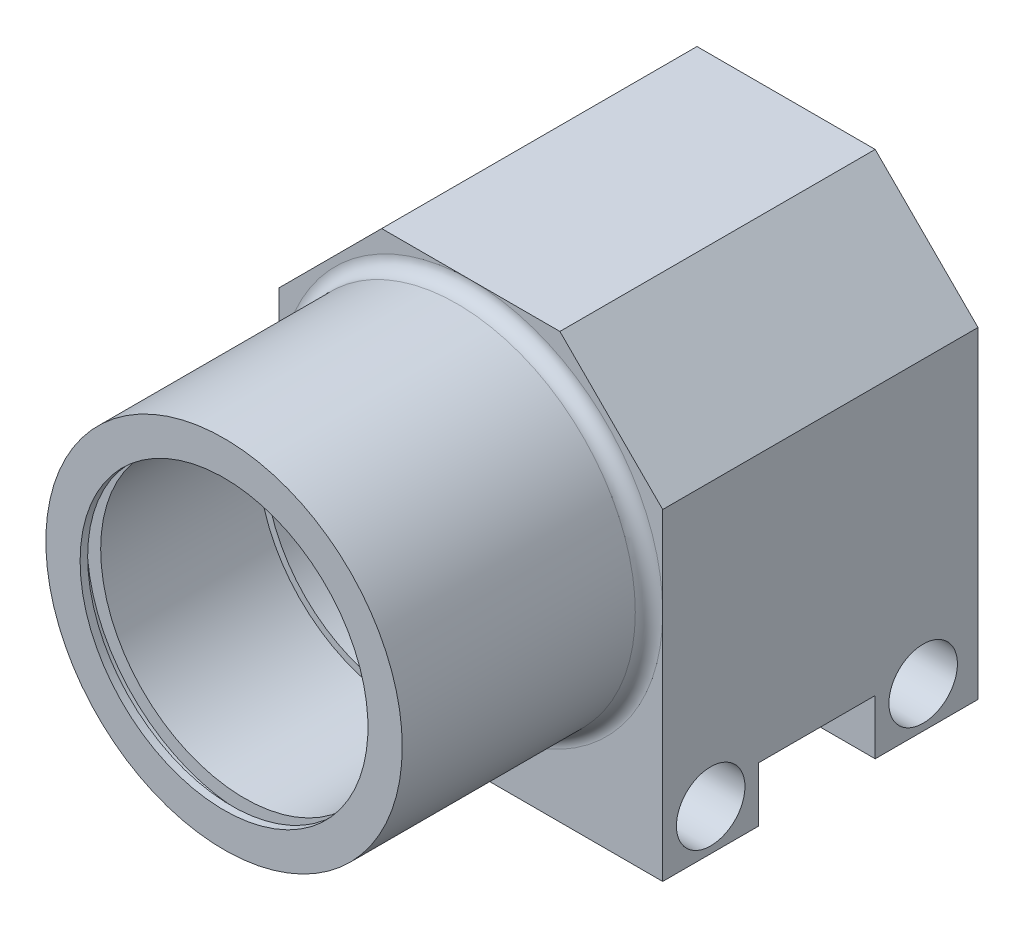
SolidWorks part; units mm, degrees
material "1060 合金"
ref_plane "前视基准面" through (0, 0, 0) normal (0, 0, 1) x (1, 0, 0)
ref_plane "上视基准面" through (0, 0, 0) normal (0, 1, 0) x (1, 0, 0)
ref_plane "右视基准面" through (0, 0, 0) normal (1, 0, 0) x (0, 0, -1)
sketch "草图1" plane through (0, 0, 0) normal (0, 0, 1) x (1, 0, 0)
  line L0 (0, -34) -> (0, 33.0223) construction
  line L1 (-28, -34) -> (28, -34)
  line L2 (-28, -34) -> (-28, 28)
  line L3 (-28, 28) -> (28, 28)
  line L4 (28, -34) -> (28, 28)
  line L5 (0, 0) -> (56.6994, 0) construction
  circle A0 centre (0, 0) radius 24 construction
  point P9 (0, 24)
  point P10 (0, -24)
  point P12 (24, 0)
  dimension "D1" = 10
  dimension "D2" = 48
  dimension "D3" = 4
  dimension "D4" = 4
extrude "凸台-拉伸1" add sketch "草图1" along normal blind 82
sketch "草图3" plane through (0, 0, 0) normal (1, 0, 0) x (0, 0, -1)
  line L0 (5.7193, 0) -> (-112.2198, 0) construction
  line L1 (0, -34) -> (0, 28) construction
  line L2 (-82, 0) -> (0, 0)
  line L3 (-82, 28) -> (-82, -34) construction
  line L4 (-82, 21) -> (-56, 21)
  line L5 (0, 0) -> (0, 23)
  line L7 (-52, 23) -> (0, 23)
  line L9 (-56, 21) -> (-56, 20)
  line L10 (-56, 20) -> (-52, 20)
  line L11 (-52, 23) -> (-52, 20)
  line L12 (-82, 0) -> (-82, 21)
  dimension "D1" = 20
  dimension "D2" = 21
  dimension "D3" = 4
  dimension "D4" = 23
  dimension "D5" = 26
revolve "切除-旋转2" cut sketch "草图3" angle 360 about L0
sketch "草图4" plane through (0, 0, 82) normal (0, 0, 1) x (1, 0, 0)
  line L0 (28, 28) -> (-28, 28) construction
  line L1 (-28, 28) -> (-28, -34) construction
  line L2 (-28, -34) -> (28, -34) construction
  line L3 (28, -34) -> (28, 28) construction
  line L4 (28, 28) -> (-28, 28)
  line L5 (-28, 28) -> (-28, -34)
  line L6 (-28, -34) -> (28, -34)
  line L7 (28, -34) -> (28, 28)
  circle A2 centre (0, 0) radius 26
  dimension "D1" = 52
chamfer "倒角1" distance 15 angle 45 2 edges at (28, 28, 41) (-28, 28, 41)
extrude "切除-拉伸1" cut sketch "草图4" against normal blind 36
hole_wizard "M4 螺纹孔1" positions "草图12" profile "草图11" tap size "M4" standard "GB"
sketch "草图12" plane through (0, 0, 0) normal (0, 0, -1) x (-1, 0, 0)
  line L0 (0, 0) -> (0, 40.8365) construction
  line L11 (0, 0) -> (18.3848, 18.3848) construction
  circle A3 centre (0, 0) radius 26
  circle A4 centre (0, 0) radius 26 construction
  point P0 (18.3848, 18.3848)
  point P116 (18.3848, -18.3848)
  point P117 (-18.3848, -18.3848)
  point P118 (-18.3848, 18.3848)
  dimension "D1" = 45
  dimension "D2" = 4
  dimension "D3" = 3
sketch "草图11" plane through (-18.3848, 18.3848, 0) normal (1, 0, 0) x (0, 1, 0)
  line L0 (0, 0) -> (0, 11.0914)
  line L1 (0, 11.0914) -> (1.65, 10.1)
  line L2 (1.65, 10.1) -> (1.65, 0)
  line L5 (1.65, 0) -> (0, 0)
  line L10 (0, 11.0914) -> (-1.65, 10.1) construction
  line L11 (0, -6.35) -> (0, 107.95) construction
  dimension "螺纹孔钻头直径" = 3.3
  dimension "螺纹孔钻头深度" = 10.1
  dimension "导头角度" = 118
cosmetic thread "孔螺蚊线5" parameters "D1"=8, "D2"=4
cosmetic thread "孔螺蚊线6" parameters "D1"=8, "D2"=4
cosmetic thread "孔螺蚊线7" parameters "D1"=8, "D2"=4
cosmetic thread "孔螺蚊线8" parameters "D1"=8, "D2"=4
sketch "草图13" plane through (28, 0, 0) normal (1, 0, 0) x (0, 0, -1)
  line L0 (-46, -34) -> (0, -34) construction
  line L1 (-46, -34) -> (-46, 13) construction
  circle A0 centre (-39, -28) radius 3.5
  circle A1 centre (-8, -28) radius 3.5
  dimension "D1" = 7
  dimension "D2" = 6
  dimension "D3" = 7
  dimension "D4" = 31
extrude "减震座孔" cut sketch "草图13" against normal through all
sketch "草图14" plane through (28, 0, 0) normal (1, 0, 0) x (0, 0, -1)
  circle A8 centre (-8, -28) radius 5
  circle A9 centre (-39, -28) radius 5
  dimension "D1" = 10
extrude "减震孔" cut sketch "草图14" against normal blind 9.5
mirror "镜向1" about plane through (0, 0, 0) normal (1, 0, 0) of "减震孔"
sketch "草图15" plane through (0, 0, 0) normal (0, 1, 0) x (1, 0, 0)
  line L0 (0, 0) -> (0, -98.0138) construction
  line L1 (-26, -82) -> (26, -82) construction
  line L2 (0, -80.9) -> (-23, -80.9)
  line L3 (0, -80.9) -> (0, -79)
  line L4 (0, -79) -> (-23, -79)
  line L5 (-23, -80.9) -> (-23, -79)
  dimension "D1" = 23
  dimension "D2" = 3
  dimension "D3" = 1.9
revolve "切除-旋转3" cut sketch "草图15" angle 360 about L0
fillet "圆角1" radius 2 1 edges at (26, 0, 46)
chamfer "倒角2" distance 1 angle 45 1 edges at (-23, 0, 0)
sketch "草图16" plane through (28, 0, 0) normal (1, 0, 0) x (0, 0, -1)
  line L0 (-46, -34) -> (0, -34) construction
  line L1 (-32, -34) -> (-15, -34)
  line L2 (-32, -34) -> (-32, -26)
  line L3 (-32, -26) -> (-15, -26)
  line L4 (-15, -34) -> (-15, -26)
  line L5 (-52, -23) -> (-1, -23) construction
  circle A0 centre (-39, -28) radius 3.5 construction
  circle A1 centre (-8, -28) radius 5 construction
  dimension "D1" = 3
  dimension "D2" = 7
  dimension "D3" = 7
extrude "减重坑" cut sketch "草图16" against normal through all
